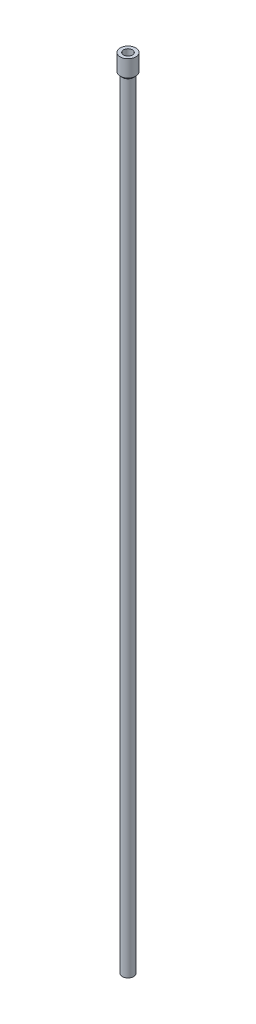
SolidWorks part; units mm, degrees
ref_plane "Front Plane" through (0, 0, 0) normal (0, 0, 1) x (1, 0, 0)
ref_plane "Top Plane" through (0, 0, 0) normal (0, 1, 0) x (1, 0, 0)
ref_plane "Right Plane" through (0, 0, 0) normal (1, 0, 0) x (0, 0, -1)
sketch "Sketch1" plane through (0, 0, 0) normal (0, 1, 0) x (1, 0, 0)
  circle A0 centre (0, 0) radius 4
  circle A1 centre (0, 0) radius 7
  dimension "D1" = 8
  dimension "D2" = 3
extrude "Boss-Extrude1" add sketch "Sketch1" along normal blind 15
sketch "Sketch2" plane through (0, 0, 0) normal (0, -1, 0) x (1, 0, 0)
  circle A0 centre (0, 0) radius 5
  dimension "D1" = 10
extrude "Boss-Extrude2" add sketch "Sketch2" along normal blind 700
chamfer "Chamfer1" distance 2 angle 45 1 edges at (0, 0, 5)
